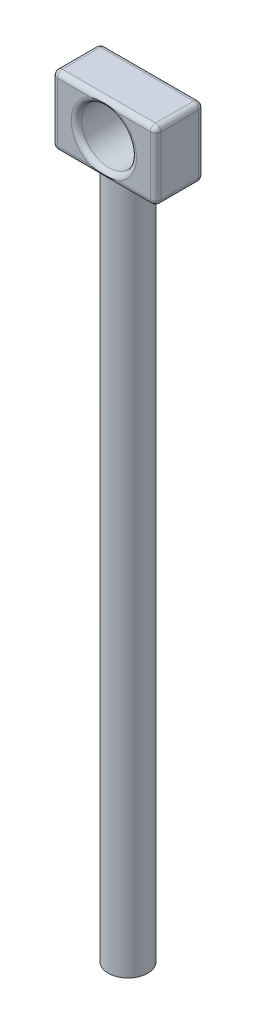
SolidWorks part; units mm, degrees
ref_plane "前视基准面" through (0, 0, 0) normal (0, 0, 1) x (1, 0, 0)
ref_plane "上视基准面" through (0, 0, 0) normal (0, 1, 0) x (1, 0, 0)
ref_plane "右视基准面" through (0, 0, 0) normal (1, 0, 0) x (0, 0, -1)
other "Configuration Table"
sketch "草图1" plane through (0, 0, 0) normal (0, 1, 0) x (1, 0, 0)
  circle A0 centre (0, 0) radius 5.75
  dimension "D1" = 11.5
extrude "凸台-拉伸1" add sketch "草图1" along normal blind 200
sketch "草图2" plane through (0, 200, 0) normal (0, 1, 0) x (1, 0, 0)
  line L1 (-15, -7) -> (15, -7)
  line L2 (-15, -7) -> (-15, 7)
  line L3 (-15, 7) -> (15, 7)
  line L4 (15, -7) -> (15, 7)
  line L5 (-15, -7) -> (15, 7) construction
  line L6 (-15, 7) -> (15, -7) construction
  point P0 (0, 0)
  dimension "D1" = 30
  dimension "D2" = 14
extrude "凸台-拉伸2" add sketch "草图2" along normal blind 20
sketch "草图3" plane through (0, 0, -7) normal (0, 0, -1) x (-1, 0, 0)
  line L0 (0, 210) -> (0, 63.5596) construction
  line L1 (15, 220) -> (15, 200) construction
  line L2 (0, 210) -> (15, 210) construction
  line L3 (-15, 200) -> (15, 200) construction
  circle A0 centre (0, 210) radius 7.95
  dimension "D1" = 15.9
extrude "切除-拉伸1" cut sketch "草图3" against normal blind 20
fillet "圆角1" radius 1.5 14 edges at (-15, 200, 0) (15, 200, 0) (-15, 220, 0) (15, 220, 0) (15, 210, -7) (0, 220, -7) (-15, 210, -7) (0, 200, -7) (-7.95, 210, -7) (-15, 210, 7) (0, 220, 7) (15, 210, 7) (0, 200, 7) (-7.95, 210, 7)
